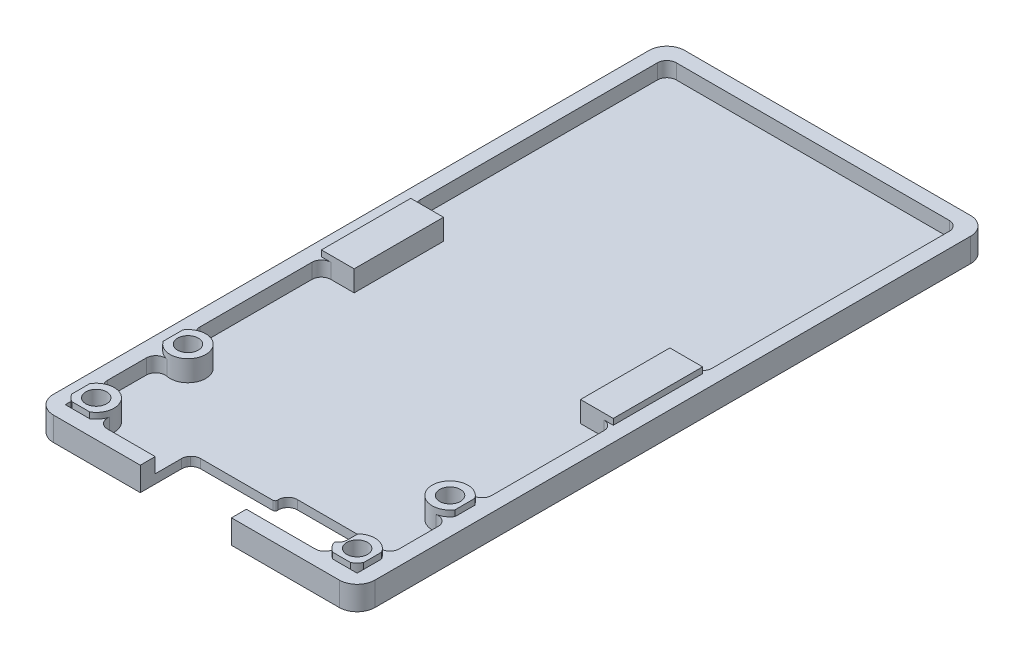
SolidWorks part; units mm, degrees
ref_plane "Front Plane" through (0, 0, 0) normal (0, 0, 1) x (1, 0, 0)
ref_plane "Top Plane" through (0, 0, 0) normal (0, 1, 0) x (1, 0, 0)
ref_plane "Right Plane" through (0, 0, 0) normal (1, 0, 0) x (0, 0, -1)
sketch "Sketch1" plane through (0, 0, 0) normal (0, 1, 0) x (1, 0, 0)
  line L1 (-24.5, -50.5) -> (24.5, -50.5)
  line L2 (-24.5, -50.5) -> (-24.5, 50.5)
  line L3 (-24.5, 50.5) -> (24.5, 50.5)
  line L4 (24.5, -50.5) -> (24.5, 50.5)
  line L5 (-24.5, -50.5) -> (24.5, 50.5) construction
  line L6 (-24.5, 50.5) -> (24.5, -50.5) construction
  point P0 (0, 0)
  dimension "D1" = 49
  dimension "D2" = 101
extrude "Boss-Extrude1" add sketch "Sketch1" along normal blind 1.5
sketch "Sketch2" plane through (0, 0, 0) normal (0, 1, 0) x (1, 0, 0)
  line L4 (24.5, -50.5) -> (24.5, 50.5)
  line L5 (24.5, 50.5) -> (-24.5, 50.5)
  line L6 (-24.5, 50.5) -> (-24.5, -50.5)
  line L7 (-24.5, -50.5) -> (24.5, -50.5)
  line L8 (24.5, -50.5) -> (24.5, 50.5)
  line L9 (24.5, 50.5) -> (-24.5, 50.5)
  line L10 (-24.5, 50.5) -> (-24.5, -50.5)
  line L11 (-24.5, -50.5) -> (24.5, -50.5)
  line L16 (27, -53) -> (27, 53)
  line L17 (27, 53) -> (-27, 53)
  line L18 (-27, 53) -> (-27, -53)
  line L19 (-27, -53) -> (27, -53)
  line L20 (27, -53) -> (27, 53)
  line L21 (27, 53) -> (-27, 53)
  line L22 (-27, 53) -> (-27, -53)
  line L23 (-27, -53) -> (27, -53)
  dimension "D1" = 0
  dimension "D2" = 2.5
extrude "Boss-Extrude2" add sketch "Sketch2" along normal blind 4
sketch "Sketch3" plane through (0, 0, 0) normal (0, 1, 0) x (1, 0, 0)
  line L0 (24.5, -50.5) -> (-24.5, -50.5) construction
  line L1 (-24.5, -50.5) -> (-24.5, 50.5) construction
  line L2 (-24.5, 50.5) -> (-24.5, -50.5) construction
  line L3 (-24.5, -30.7417) -> (-24.5, -34.0583)
  line L4 (-24.5, -7.5) -> (-19, -7.5)
  line L5 (-24.5, -7.5) -> (-24.5, 7.5)
  line L6 (-24.5, 7.5) -> (-19, 7.5)
  line L7 (-19, -7.5) -> (-19, 7.5)
  line L8 (-24.5, -46.4033) -> (-24.5, -49.3967)
  line L9 (-24.5, 50.5) -> (-24.5, -50.5) construction
  line L10 (-23.3967, -50.5) -> (-20.4033, -50.5)
  line L11 (-24.5, -50.5) -> (24.5, -50.5) construction
  arc A0 (-24.5, -49.3967) -> (-23.3967, -50.5) centre (-21.9, -47.9) ccw
  arc A1 (-24.5, -34.0583) -> (-24.5, -30.7417) centre (-22, -32.4) ccw
  arc A2 (-20.4033, -50.5) -> (-24.5, -46.4033) centre (-21.9, -47.9) ccw
  point P15 (-19, 0)
  dimension "D2" = 2.6
  dimension "D5" = 6
  dimension "D7" = 6
  dimension "D1" = 2.6
  dimension "D3" = 2.5
  dimension "D4" = 18.1
  dimension "D6" = 15
extrude "Boss-Extrude3" add sketch "Sketch3" along normal offset from surface (5 mm away) 1 up to face at (0, 4, 0) offset beyond the face yes
mirror "Mirror1" about plane through (0, 0, 0) normal (1, 0, 0) of "Boss-Extrude3"
sketch "Sketch4" plane through (0, 5, 0) normal (0, 1, 0) x (1, 0, 0)
  circle A0 centre (-21.9, -47.9) radius 1.75
  circle A1 centre (21.9, -47.9) radius 1.75
  dimension "D1" = 3.5
  dimension "D2" = 3.5
extrude "Cut-Extrude1" cut sketch "Sketch4" against normal blind 4.25
sketch "Sketch5" plane through (0, 5, 0) normal (0, 1, 0) x (1, 0, 0)
  circle A0 centre (-22, -32.4) radius 1.75
  circle A1 centre (22, -32.4) radius 1.75
  dimension "D1" = 3.5
  dimension "D2" = 3.5
extrude "Cut-Extrude2" cut sketch "Sketch5" against normal blind 4.25
sketch "Sketch6" plane through (0, 0, 0) normal (0, 1, 0) x (1, 0, 0)
  line L1 (-9, -45) -> (5.5, -45)
  line L2 (-9, -45) -> (-9, -52.3)
  line L3 (-9, -52.3) -> (5.5, -52.3)
  line L4 (5.5, -45) -> (5.5, -52.3)
  line L8 (-23.3967, -50.5) -> (20.4033, -50.5) construction
  line L10 (24.5, -46.4033) -> (24.5, -34.0583) construction
  line L11 (-24.5, -34.0583) -> (-24.5, -46.4033) construction
  line L13 (-27, -53) -> (27, -53) construction
  dimension "D1" = 15.5
  dimension "D2" = 19
  dimension "D3" = 0.7
  dimension "D4" = 5.5
extrude "Cut-Extrude3" cut sketch "Sketch6" along normal through all
sketch "Sketch7" plane through (0, 0, 0) normal (0, 1, 0) x (1, 0, 0)
  line L0 (-27, -53) -> (27, -53) construction
  line L1 (19.3, -48.7) -> (5.5, -48.7)
  line L2 (19.3, -48.7) -> (19.3, -42.7)
  line L3 (19.3, -42.7) -> (5.5, -42.7)
  line L4 (5.5, -48.7) -> (5.5, -42.7)
  line L5 (5.5, -52.3) -> (5.5, -45) construction
  line L7 (27, -53) -> (27, 53) construction
  point P4 (19.3, -45.7)
  point P10 (12.4, -42.7)
  dimension "D1" = 13.8
  dimension "D2" = 7.3
  dimension "D3" = 6
  dimension "D5" = 14.6
extrude "Cut-Extrude4" cut sketch "Sketch7" along normal through all
fillet "Fillet1" radius 3 4 edges at (-27, 2, 53) (27, 2, 53) (27, 2, -53) (-27, 2, -53)
sketch "Sketch9" plane through (0, 0, 0) normal (0, 1, 0) x (1, 0, 0)
  line L1 (-7.8144, -44.472) -> (4.3144, -44.472)
  line L2 (-9.4019, -46.0595) -> (-9.4019, -53)
  line L4 (5.9019, -50.6653) -> (5.9019, -53)
  line L5 (5.5, -45) -> (-9, -45) construction
  line L6 (-24, -53) -> (24, -53) construction
  line L7 (-9.9507, -45.9507) -> (-6.3158, -42.3158) construction
  line L8 (19.8536, -47.4878) -> (19.8536, -43.9058)
  line L9 (7.4894, -49.0778) -> (18.2636, -49.0778)
  line L10 (18.2636, -42.3158) -> (6.2841, -42.3158)
  line L11 (4.6941, -43.9058) -> (4.6941, -44.0923)
  line L12 (14.9847, -53.0153) -> (27.5336, -40.4664) construction
  line L13 (5.5, -48.7) -> (19.0086, -48.7) construction
  line L14 (-9.4019, -53) -> (5.9019, -53)
  line L15 (5.5, -52.3) -> (-9, -52.3) construction
  arc A3 (-7.8144, -44.472) -> (-9.4019, -46.0595) centre (-7.8144, -46.0595) ccw
  arc A4 (5.9019, -50.6653) -> (7.4894, -49.0778) centre (7.4894, -50.6653) cw
  arc A5 (18.2636, -49.0778) -> (19.8536, -47.4878) centre (18.2636, -47.4878) ccw
  arc A6 (19.8536, -43.9058) -> (18.2636, -42.3158) centre (18.2636, -43.9058) ccw
  arc A7 (6.2841, -42.3158) -> (4.6941, -43.9058) centre (6.2841, -43.9058) ccw
  arc A8 (4.6941, -44.0923) -> (4.3144, -44.472) centre (4.3144, -44.0923) cw
  point P0 (-1.75, -48.65)
  point P4 (-1.75, -45)
  point P17 (-1.75, -52.3)
  point P21 (-1.75, -44.472)
  point P23 (-1.75, -53)
  dimension "D1" = 1.5875
  dimension "D4" = 1.59
  dimension "D2" = 135
  dimension "D3" = 45
  dimension "D5" = 1.5949
  dimension "D6" = 1.59
  dimension "D7" = 1.4383
  dimension "D8" = 1.59
extrude "Cut-Extrude5" cut sketch "Sketch9" along normal through all
fillet "Fillet2" radius 1.5875 14 edges at (20.4033, 2.75, 50.5) (-20.4033, 2.75, 50.5) (-24.5, 2.75, 34.0583) (-24.5, 2.75, 30.7417) (-24.5, 2.75, 46.4033) (24.5, 2.75, 46.4033) (24.5, 2.75, 34.0583) (24.5, 2.75, 30.7417) (24.5, 2.75, -7.5) (24.5, 2.75, 7.5) (-24.5, 2.75, 7.5) (-24.5, 2.75, -7.5) (24.5, 2.75, -50.5) (-24.5, 2.75, -50.5)
sketch "Sketch11" plane through (0, 0, 0) normal (0, 1, 0) x (1, 0, 0)
  line L0 (24, 53) -> (-24, 53) construction
  line L1 (27, -50) -> (27, 50) construction
  line L2 (5.9019, -53) -> (24, -53) construction
  line L3 (-24, -53) -> (-9.4019, -53) construction
  line L4 (-27, 50) -> (-27, -50) construction
  line L5 (24, 53) -> (-24, 53)
  line L6 (27, -50) -> (27, 50)
  line L7 (5.9019, -53) -> (24, -53)
  line L8 (-24, -53) -> (-9.4019, -53)
  line L9 (-27, 50) -> (-27, -50)
  line L10 (-9.4019, -53) -> (5.9019, -53)
  arc A0 (-24, 53) -> (-27, 50) centre (-24, 50) ccw construction
  arc A1 (27, 50) -> (24, 53) centre (24, 50) ccw construction
  arc A2 (24, -53) -> (27, -50) centre (24, -50) ccw construction
  arc A3 (-27, -50) -> (-24, -53) centre (-24, -50) ccw construction
  arc A4 (-24, 53) -> (-27, 50) centre (-24, 50) ccw
  arc A5 (27, 50) -> (24, 53) centre (24, 50) ccw
  arc A6 (24, -53) -> (27, -50) centre (24, -50) ccw
  arc A7 (-27, -50) -> (-24, -53) centre (-24, -50) ccw
sketch "Sketch12" plane through (0, 0, 0) normal (0, 1, 0) x (1, 0, 0)
  line L0 (5.9019, -53) -> (24, -53) construction
  line L1 (-44, 141.873) -> (44, 141.873)
  line L2 (-44, 141.873) -> (-44, -53.127)
  line L3 (-44, -53.127) -> (44, -53.127)
  line L4 (44, 141.873) -> (44, -53.127)
  line L5 (-44, 141.873) -> (44, -53.127) construction
  line L6 (-44, -53.127) -> (44, 141.873) construction
  point P0 (0, 44.373)
  point P6 (0, -53.127)
  dimension "D1" = 88.0001
  dimension "D2" = 195
  dimension "D3" = 0.127
sketch "Sketch13" plane through (0, 0, 0) normal (0, 1, 0) x (1, 0, 0)
  line L0 (-44, 91.073) -> (44, 91.073)
  line L1 (-44, 141.873) -> (-44, -53.127) construction
  line L2 (44, 141.873) -> (44, -53.127) construction
  line L3 (-44, 141.873) -> (44, 141.873) construction
  line L4 (44, 91.073) -> (44, -53.127)
  line L5 (44, -53.127) -> (-44, -53.127)
  line L6 (-44, -53.127) -> (-44, 91.073)
  dimension "D1" = 50.8
sketch "Sketch15" plane through (0, 0, 0) normal (0, 1, 0) x (1, 0, 0)
  line L0 (-44, 72.023) -> (44, 72.023)
  line L1 (-44, 141.873) -> (-44, -53.127) construction
  line L2 (44, 141.873) -> (44, -53.127) construction
  line L3 (-44, 91.073) -> (44, 91.073) construction
  line L4 (-44, 72.023) -> (-44, -53.127)
  line L5 (-44, -53.127) -> (44, -53.127)
  line L6 (44, -53.127) -> (44, 72.023)
  dimension "D1" = 19.05
sketch "Sketch17" plane through (0, 0, 0) normal (0, 1, 0) x (1, 0, 0)
  line L0 (-44, 59.323) -> (44, 59.323)
  line L1 (-44, 141.873) -> (-44, -53.127) construction
  line L2 (44, 141.873) -> (44, -53.127) construction
  line L3 (-44, 72.023) -> (44, 72.023) construction
  line L4 (-44, 59.323) -> (-44, -53.127)
  line L5 (-44, -53.127) -> (44, -53.127)
  line L6 (44, -53.127) -> (44, 59.323)
  dimension "D1" = 12.7
sketch "Sketch18" plane through (0, 0, 0) normal (0, 1, 0) x (1, 0, 0)
  line L0 (-24, -53) -> (-9.4019, -53) construction
  line L1 (-31.8999, -53) -> (31.8999, -53)
  line L2 (-31.8999, -53) -> (-31.8999, 59.088)
  line L3 (-31.8999, 59.088) -> (31.8999, 59.088)
  line L4 (31.8999, -53) -> (31.8999, 59.088)
  line L5 (-31.8999, -53) -> (31.8999, 59.088) construction
  line L6 (-31.8999, 59.088) -> (31.8999, -53) construction
  point P0 (0, 3.044)
